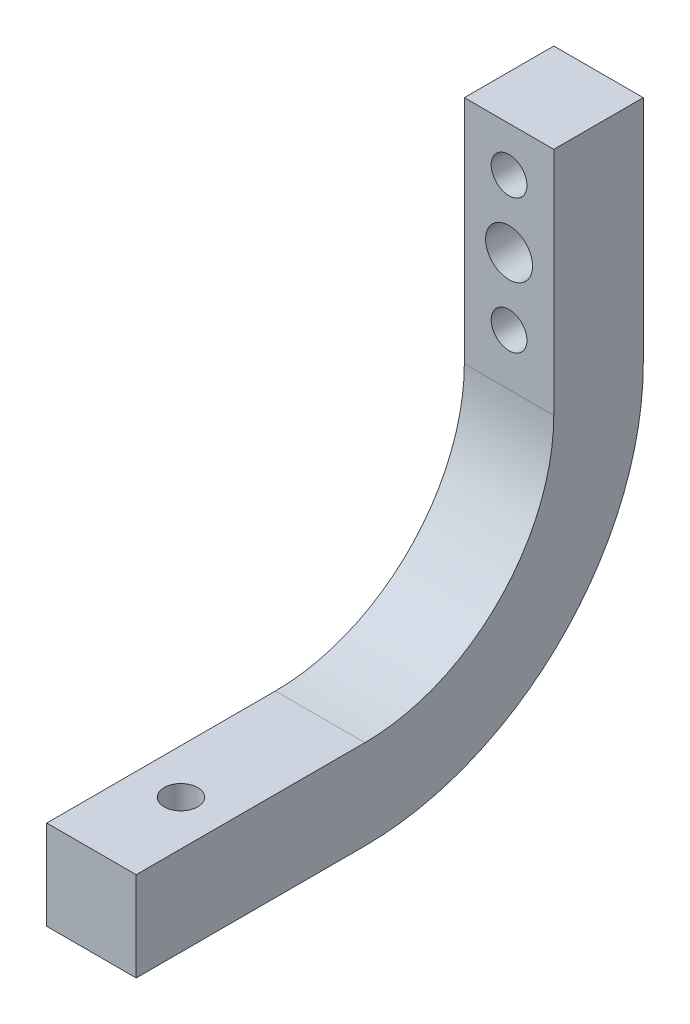
SolidWorks part; units mm, degrees
ref_plane "Front Plane" through (0, 0, 0) normal (0, 0, 1) x (1, 0, 0)
ref_plane "Top Plane" through (0, 0, 0) normal (0, 1, 0) x (1, 0, 0)
ref_plane "Right Plane" through (0, 0, 0) normal (1, 0, 0) x (0, 0, -1)
ref_axis "Z" through (0, 0, 47.607) along (0, 0, -1)
sketch "Sketch1" plane through (0, 0, 0) normal (1, 0, 0) x (0, 0, -1)
  line L0 (-8, 10) -> (0, 10)
  line L1 (0, 10) -> (0, -10.6067)
  line L2 (0, -18) -> (-17.5, -35.5) construction
  line L3 (-24.8933, -35.5) -> (-37.34, -35.5)
  line L4 (-37.34, -35.5) -> (-37.34, -27.5) construction
  line L5 (-37.34, -27.5) -> (-24.8933, -27.5)
  line L6 (-20.8137, -27.5) -> (-8, -14.6863) construction
  line L7 (-8, -10.6067) -> (-8, 10)
  line L8 (-14.4069, -21.0931) -> (-8.75, -26.75) construction
  line L9 (-24.8933, -27.5) -> (-20.8137, -27.5) construction
  line L10 (-37.34, -27.5) -> (-45.34, -27.5)
  line L11 (-37.34, -27.5) -> (-37.34, -35.5) construction
  line L12 (-37.34, -35.5) -> (-45.34, -35.5)
  line L13 (-45.34, -27.5) -> (-45.34, -35.5)
  line L14 (-8, -14.6863) -> (-8, -10.6067) construction
  line L15 (0, -10.6067) -> (0, -18) construction
  line L16 (-17.5, -35.5) -> (-24.8933, -35.5) construction
  arc A0 (-24.8933, -27.5) -> (-8, -10.6067) centre (-24.8933, -10.6067) ccw
  arc A1 (-24.8933, -35.5) -> (0, -10.6067) centre (-24.8933, -10.6067) ccw
  dimension "D1" = 8
  dimension "D2" = 37.34
  dimension "D3" = 35.5
  dimension "D4" = 10
  dimension "D5" = 135
  dimension "D6" = 17.5
  dimension "D7" = 8
  dimension "D8" = 12.4467
extrude "Boss-Extrude1" add sketch "Sketch1" along normal blind 4 and the other way blind 4
sketch "Sketch3" plane through (0, -27.5, 0) normal (0, 1, 0) x (1, 0, 0)
  line L0 (-55, 0) -> (55, 0) construction
  line L1 (0, -55) -> (0, 55) construction
  circle A0 centre (0, -37.34) radius 1.5
  dimension "D2" = 3
  dimension "D1" = 37.34
extrude "Cut-Extrude1" cut sketch "Sketch3" against normal through all
sketch "Sketch4" plane through (0, 0, 8) normal (0, 0, 1) x (1, 0, 0)
  line L0 (0, -6) -> (0, 6) construction
  circle A0 centre (0, 0) radius 2.1
  circle A1 centre (0, 6) radius 1.6
  circle A2 centre (0, -6) radius 1.6
  dimension "D1" = 4.2
  dimension "D3" = 3.2
  dimension "D2" = 12
extrude "Cut-Extrude2" cut sketch "Sketch4" against normal through all both and the other way through all
ref_axis "Axis1" through (0, -27.5, 37.34) along (0, 1, 0)
equation "\"rbracket-width\"=8"
equation "\"D1@Boss-Extrude1\"=\"rbracket-width\"/2"
equation "\"D2@Boss-Extrude1\"=\"rbracket-width\"/2"
equation "\"EyeCaptureRadius\"= ( \"EyeDiameter\" + \"EyeClearance\" ) / 2"
equation "\"rbracket_planetocenterline_dist\"= \"BasePlaneDistance\""
equation "\"D2@Sketch1\"=\"rbracket_planetocenterline_dist\""
equation "\"EyeDiameter\" = 35"
equation "\"BasePlaneDistance\" = \"EyeDiameter\"/2+19.84"
equation "\"EyeClearance\" = 2"
equation "\"D1@Sketch1\"=\"rbracket-width\""
equation "\"D3@Sketch1\"=(\"EyeDiameter\"+\"EyeClearance\"+\"EyeClearance\")/2 + \"L2Thickness\" + \"rbracket-width\""
equation "\"D4@Sketch1\"= 10"
equation "\"D6@Sketch1\"=\"EyeDiameter\"/2"
equation "\"D7@Sketch1\"=\"rbracket-width\""
equation "\"D1@Sketch3\"=\"BasePlaneDistance\""
equation "\"L2Thickness\" = 8"
equation "\"D8@Sketch1\"=\"rbracket_planetocenterline_dist\"/3"
